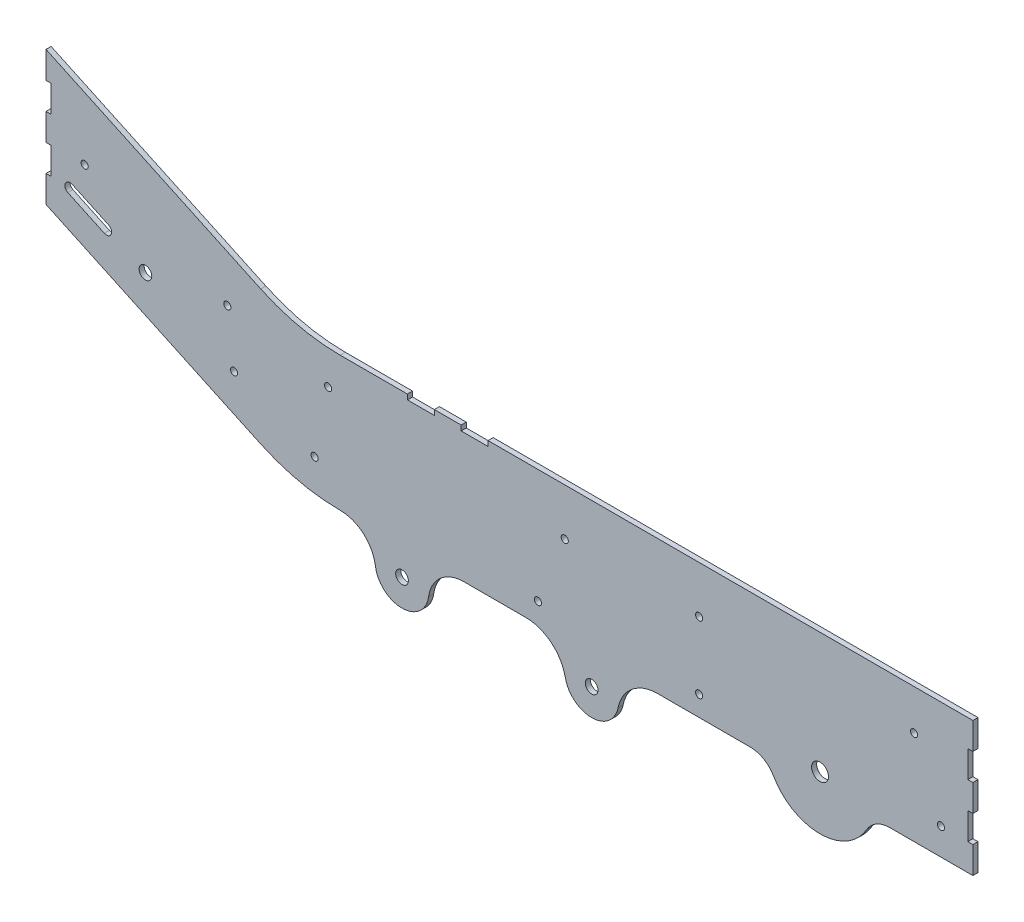
SolidWorks part; units mm, degrees
material "1060 Alloy"
ref_plane "Front Plane" through (0, 0, 0) normal (0, 0, 1) x (1, 0, 0)
ref_plane "Top Plane" through (0, 0, 0) normal (0, 1, 0) x (1, 0, 0)
ref_plane "Right Plane" through (0, 0, 0) normal (1, 0, 0) x (0, 0, -1)
sketch "standoff holes lower" plane through (0, 0, 0) normal (0, 0, 1) x (1, 0, 0)
  circle A7 centre (95.25, 85.725) radius 3.3782
  circle A8 centre (95.25, 12.7) radius 3.3782
  circle A9 centre (171.45, 12.7) radius 3.3782
  circle A10 centre (171.45, 85.725) radius 3.3782
  circle A12 centre (298.45, 12.7) radius 3.3782
  circle A13 centre (450.85, 85.725) radius 3.3782
  circle A16 centre (273.05, 85.725) radius 3.3782
  point P21 (0, 0)
sketch "axle holes lower" plane through (0, 0, 0) normal (0, 0, 1) x (1, 0, 0)
  line L10 (514.35, 98.425) -> (75.4368, 98.425) construction
  line L11 (66.0749, 94.3067) -> (3.3381, 25.8666) construction
  line L12 (0, 17.2849) -> (0, 12.7) construction
  line L13 (12.7, 0) -> (514.35, 0) construction
  line L14 (527.05, 12.7) -> (527.05, 85.725) construction
  circle A1 centre (247.65, 15.24) radius 4.826
  circle A4 centre (19.05, 19.05) radius 4.826
  arc A10 (527.05, 85.725) -> (514.35, 98.425) centre (514.35, 85.725) ccw construction
  arc A11 (75.4368, 98.425) -> (66.0749, 94.3067) centre (75.4368, 85.725) ccw construction
  arc A12 (3.3381, 25.8666) -> (0, 17.2849) centre (12.7, 17.2849) ccw construction
  arc A13 (0, 12.7) -> (12.7, 0) centre (12.7, 12.7) ccw construction
  arc A14 (514.35, 0) -> (527.05, 12.7) centre (514.35, 12.7) ccw construction
  circle A15 centre (476.25, 19.05) radius 4.826
sketch "lower box" plane through (0, 0, 0) normal (0, 0, 1) x (1, 0, 0)
  line L1 (622.3, 0) -> (-254, 0) construction
  line L2 (622.3, 0) -> (622.3, 25.4) construction
  line L3 (622.3, 127) -> (-254, 127) construction
  line L4 (-254, 0) -> (-254, 127) construction
  line L6 (527.05, 12.7) -> (527.05, 85.725) construction
  line L7 (622.3, 101.6) -> (622.3, 127) construction
  line L8 (622.3, 101.6) -> (617.474, 101.6) construction
  line L10 (622.3, 76.2) -> (617.474, 76.2) construction
  line L11 (617.474, 101.6) -> (617.474, 76.2) construction
  line L12 (622.3, 50.8) -> (617.474, 50.8) construction
  line L14 (622.3, 25.4) -> (617.474, 25.4) construction
  line L15 (617.474, 50.8) -> (617.474, 25.4) construction
  line L16 (622.3, 50.8) -> (622.3, 76.2) construction
  dimension "D1" = 127
  dimension "D2" = 876.3
  dimension "D3" = 95.25
  dimension "D4" = 4.826
sketch "alxe holes upper" plane through (0, 0, 0) normal (0, 0, 1) x (1, 0, 0)
  line L0 (-219.7848, 130.4205) -> (-230.5193, 107.4003) construction
  line L1 (-230.5193, 107.4003) -> (8.3155, -3.9702) construction
  line L3 (8.3155, -3.9702) -> (19.05, 19.05) construction
  line L4 (622.3, 0) -> (-254, 0) construction
  circle A0 centre (19.05, 19.05) radius 4.826 construction
  circle A2 centre (-219.7848, 130.4205) radius 4.826
  circle A3 centre (19.05, 19.05) radius 4.826
  dimension "D4" = 25
  dimension "D1" = 25.4
  dimension "D2" = 25.4
  dimension "D3" = 263.525
sketch "standoff holes upper" plane through (0, 0, 0) normal (0, 0, 1) x (1, 0, 0)
  line L0 (-162.9561, 84.3028) -> (-166.1764, 77.3967) construction
  line L1 (-226.6865, 105.613) -> (11.2395, -5.3337) construction
  line L4 (-37.2808, 64.9356) -> (-55.5295, 25.8012) construction
  line L5 (-230.5193, 107.4003) -> (8.3155, -3.9702) construction
  circle A2 centre (-162.9561, 84.3028) radius 3.3782
  circle A3 centre (-37.2808, 64.9356) radius 3.3782
  dimension "D2" = 7.62
  dimension "D1" = 43.18
sketch "upper shadow" plane through (0, 0, 0) normal (0, 0, 1) x (1, 0, 0)
  line L0 (-230.5193, 107.4003) -> (8.3155, -3.9702) construction
  line L4 (33.2535, 40.1076) -> (-204.2179, 150.8423) construction
  line L5 (-230.5193, 107.4003) -> (8.3155, -3.9702) construction
  arc A4 (8.3155, -3.9702) -> (33.2535, 40.1076) centre (19.05, 19.05) ccw construction
  arc A5 (-204.2179, 150.8423) -> (-230.5193, 107.4003) centre (-216.8161, 128.7868) ccw construction
  dimension "D1" = 25.4
  dimension "D2" = 25.4
sketch "upper box" plane through (0, 0, 0) normal (0, 0, 1) x (1, 0, 0)
  line L0 (-15.224, 0) -> (-254, 111.3431) construction
  line L1 (622.3, 0) -> (-254, 0) construction
  line L2 (-254, 111.3431) -> (-254, 136.7431) construction
  line L3 (-254, 238.3431) -> (257.1283, 0) construction
  line L4 (12.7, 0) -> (514.35, 0) construction
  line L5 (-254, 0) -> (-254, 127) construction
  line L6 (-230.5193, 107.4003) -> (8.3155, -3.9702) construction
  line L7 (-254, 212.9431) -> (-254, 238.3431) construction
  line L8 (-254, 212.9431) -> (-249.174, 212.9431) construction
  line L9 (-254, 162.1431) -> (-254, 187.5431) construction
  line L10 (-254, 187.5431) -> (-249.174, 187.5431) construction
  line L11 (-249.174, 212.9431) -> (-249.174, 187.5431) construction
  line L12 (-254, 162.1431) -> (-249.174, 162.1431) construction
  line L14 (-254, 136.7431) -> (-249.174, 136.7431) construction
  line L15 (-249.174, 162.1431) -> (-249.174, 136.7431) construction
  dimension "D1" = 127
  dimension "D2" = 6.35
  dimension "D3" = 4.826
sketch "outer face" plane through (0, 0, 0) normal (0, 0, 1) x (1, 0, 0)
  line L0 (622.3, 0) -> (-254, 0) construction
  line L1 (622.3, 0) -> (622.3, 25.4) construction
  line L2 (622.3, 25.4) -> (617.474, 25.4) construction
  line L3 (617.474, 50.8) -> (617.474, 25.4) construction
  line L4 (622.3, 50.8) -> (617.474, 50.8) construction
  line L5 (622.3, 50.8) -> (622.3, 76.2) construction
  line L6 (622.3, 76.2) -> (617.474, 76.2) construction
  line L7 (617.474, 101.6) -> (617.474, 76.2) construction
  line L8 (622.3, 101.6) -> (622.3, 127) construction
  line L9 (622.3, 101.6) -> (617.474, 101.6) construction
  line L10 (622.3, 127) -> (-254, 127) construction
  line L11 (-254, 238.3431) -> (257.1283, 0) construction
  line L12 (-254, 212.9431) -> (-254, 238.3431) construction
  line L13 (-254, 212.9431) -> (-249.174, 212.9431) construction
  line L14 (-249.174, 212.9431) -> (-249.174, 187.5431) construction
  line L15 (-249.174, 162.1431) -> (-249.174, 136.7431) construction
  line L16 (-254, 136.7431) -> (-249.174, 136.7431) construction
  line L17 (-254, 111.3431) -> (-254, 136.7431) construction
  line L18 (-15.224, 0) -> (-254, 111.3431) construction
  line L19 (-254, 162.1431) -> (-249.174, 162.1431) construction
  line L20 (-254, 162.1431) -> (-254, 187.5431) construction
  line L21 (-254, 187.5431) -> (-249.174, 187.5431) construction
  line L22 (622.3, 0) -> (24.1933, 0)
  line L23 (622.3, 0) -> (622.3, 25.4)
  line L24 (622.3, 25.4) -> (617.474, 25.4)
  line L25 (617.474, 50.8) -> (617.474, 25.4)
  line L26 (622.3, 50.8) -> (617.474, 50.8)
  line L27 (622.3, 50.8) -> (622.3, 76.2)
  line L28 (622.3, 76.2) -> (617.474, 76.2)
  line L29 (617.474, 101.6) -> (617.474, 76.2)
  line L30 (622.3, 101.6) -> (622.3, 127)
  line L31 (622.3, 101.6) -> (617.474, 101.6)
  line L32 (622.3, 127) -> (24.1933, 127)
  line L33 (-254, 238.3431) -> (-50.9483, 143.6585)
  line L34 (-254, 212.9431) -> (-254, 238.3431)
  line L35 (-254, 212.9431) -> (-249.174, 212.9431)
  line L36 (-249.174, 212.9431) -> (-249.174, 187.5431)
  line L37 (-249.174, 162.1431) -> (-249.174, 136.7431)
  line L38 (-254, 136.7431) -> (-249.174, 136.7431)
  line L39 (-254, 111.3431) -> (-254, 136.7431)
  line L40 (-50.9483, 16.6585) -> (-254, 111.3431)
  line L41 (-254, 162.1431) -> (-249.174, 162.1431)
  line L42 (-254, 162.1431) -> (-254, 187.5431)
  line L43 (-254, 187.5431) -> (-249.174, 187.5431)
  arc A0 (-50.9483, 16.6585) -> (24.1933, 0) centre (24.1933, 177.8) ccw
  arc A1 (24.1933, 127) -> (-50.9483, 143.6585) centre (24.1933, 304.8) cw
  dimension "D1" = 177.8
extrude "Boss-Extrude1" add sketch "outer face" along normal blind 4.826
sketch "Sketch5" plane through (0, 0, 4.826) normal (0, 0, 1) x (1, 0, 0)
  line L1 (-249.174, 162.1431) -> (-249.174, 136.7431) construction
  line L2 (622.3, 127) -> (24.1933, 127) construction
  line L4 (617.474, 76.2) -> (617.474, 101.6) construction
  line L5 (622.3, 127) -> (24.1933, 127) construction
  line L6 (414.2486, -29.6609) -> (414.2486, 95.7516) construction
  line L7 (24.1933, 0) -> (622.3, 0) construction
  line L8 (617.474, 25.4) -> (617.474, 50.8) construction
  circle A9 centre (-76.2, 63.5) radius 3.3782
  circle A10 centre (-82.55, 114.3) radius 3.3782
  circle A11 centre (592.074, 25.4) radius 3.3782
  circle A12 centre (0, 31.75) radius 3.3782
  circle A13 centre (211.0486, 19.05) radius 3.3782
  circle A14 centre (236.4486, 82.55) radius 3.3782
  circle A15 centre (363.4486, 82.55) radius 3.3782
  circle A16 centre (363.4486, 19.05) radius 3.3782
  circle A17 centre (566.674, 88.9) radius 3.3782
  circle A18 centre (12.7, 95.25) radius 3.3782
  circle A19 centre (-217.424, 162.1431) radius 3.3782
  dimension "D9" = 127
  dimension "D10" = 152.4
  dimension "D11" = 19.05
  dimension "D12" = 44.45
  dimension "D13" = 6.7564
  dimension "D7" = 19.05
  dimension "D14" = 25.4
  dimension "D15" = 25.4
  dimension "D17" = 31.75
  dimension "D16" = 82.55
  dimension "D18" = 82.55
  dimension "D19" = 76.2
  dimension "D20" = 31.75
  dimension "D21" = 31.75
  dimension "D22" = 50.8
  dimension "D23" = 63.5
  dimension "D24" = 12.7
  dimension "D3" = 38.1
  dimension "D4" = 50.8
  dimension "D5" = 44.45
  dimension "D6" = 50.8
  dimension "D8" = 50.8
extrude "standoff hole" cut sketch "Sketch5" against normal through all
sketch "Sketch6" plane through (0, 0, 4.826) normal (0, 0, 1) x (1, 0, 0)
  circle A0 centre (-219.7848, 130.4205) radius 4.826 construction
  circle A1 centre (19.05, 19.05) radius 4.826 construction
  circle A2 centre (247.65, 15.24) radius 4.826 construction
  circle A4 centre (-219.7848, 130.4205) radius 4.826
  circle A5 centre (19.05, 19.05) radius 4.826 construction
  circle A6 centre (247.65, 15.24) radius 4.826 construction
extrude "axle holes" cut sketch "Sketch6" against normal through all
sketch "Sketch7" plane through (0, 0, 4.826) normal (0, 0, 1) x (1, 0, 0)
  line L0 (-231.2949, 135.7877) -> (-196.7645, 119.686) construction
  line L1 (-229.2553, 140.1616) -> (-194.725, 124.0598)
  line L2 (-233.3344, 131.4139) -> (-198.8041, 115.3121)
  line L3 (-230.5193, 107.4003) -> (8.3155, -3.9702) construction
  circle A0 centre (-219.7848, 130.4205) radius 4.826 construction
  circle A1 centre (-219.7848, 130.4205) radius 4.826
  arc A2 (-229.2553, 140.1616) -> (-233.3344, 131.4139) centre (-231.2949, 135.7877) ccw
  arc A3 (-198.8041, 115.3121) -> (-194.725, 124.0598) centre (-196.7645, 119.686) ccw
  point P5 (-214.0297, 127.7369)
  circle M6 centre (-219.7848, 130.4205) radius 4.826
  dimension "D1" = 38.1
  dimension "D2" = 12.7
extrude "front slot" cut sketch "Sketch7" against normal through all contours L1 A2 L2 A1 M6 | L2 A3 L1 region at (-228.975, 134.706, 4.826) region at (-204.8394, 123.4514, 4.826)
sketch "Sketch8" plane through (0, 0, 4.826) normal (0, 0, 1) x (1, 0, 0)
  line L0 (113.0933, 127) -> (113.0933, 122.174) construction
  line L1 (87.6933, 122.174) -> (113.0933, 122.174)
  line L2 (87.6933, 122.174) -> (87.6933, 127)
  line L3 (87.6933, 127) -> (113.0933, 127)
  line L4 (113.0933, 122.174) -> (113.0933, 127)
  line L5 (622.3, 127) -> (24.1933, 127) construction
  line L6 (113.0933, 122.174) -> (138.4933, 122.174) construction
  line L7 (138.4933, 122.174) -> (163.8933, 122.174)
  line L8 (138.4933, 122.174) -> (138.4933, 127)
  line L9 (138.4933, 127) -> (163.8933, 127)
  line L10 (163.8933, 122.174) -> (163.8933, 127)
  line L11 (62.2933, 122.174) -> (189.2933, 122.174)
  line L12 (62.2933, 122.174) -> (62.2933, 127)
  line L13 (62.2933, 127) -> (189.2933, 127)
  line L14 (189.2933, 122.174) -> (189.2933, 127)
  line L15 (163.8933, 127) -> (163.8933, 122.174) construction
  point P18 (125.7933, 122.174)
  point P19 (125.7933, 122.174)
  line M29 (622.3, 127) -> (24.1933, 127)
  dimension "D1" = 127
extrude "top slots" cut sketch "Sketch8" against normal through all contours L1 L4 L2 M29 | L7 L10 L8 M29 region at (100.3933, 124.587, 4.826) region at (151.1933, 124.587, 4.826)
sketch "Sketch9" plane through (0, 0, 4.826) normal (0, 0, 1) x (1, 0, 0)
  line L0 (365.4629, -63.5) -> (553.974, -63.5) construction
  line L1 (24.1933, 0) -> (622.3, 0) construction
  line L3 (553.974, -63.5) -> (553.974, 63.787) construction
  line L4 (617.474, 25.4) -> (617.474, 50.8) construction
  line L5 (24.1933, 0) -> (622.3, 0)
  circle A0 centre (477.774, 12.7) radius 76.2 construction
  circle A1 centre (477.774, 12.7) radius 8
  arc A2 (433.7799, -12.7) -> (521.7681, -12.7) centre (477.774, 12.7) ccw
  arc A3 (543.7651, 0) -> (521.7681, -12.7) centre (543.7651, -25.4) ccw
  arc A4 (433.7799, -12.7) -> (411.7829, 0) centre (411.7829, -25.4) ccw
  dimension "D1" = 152.4
  dimension "D4" = 16
  dimension "D5" = 50.8
  dimension "D6" = 25.4
  dimension "D7" = 25.4
  dimension "D2" = 63.5
  dimension "D3" = 63.5
extrude "back axle extension" add sketch "Sketch9" against normal up to surface (4.826 mm away) contours A4 A2 A3 L5 region at (477.774, -15.4671, 4.826) up to face at (-214.0297, 127.7369, 0)
sketch "Sketch11" plane through (0, 0, 4.826) normal (0, 0, 1) x (1, 0, 0)
  line L0 (24.1933, 0) -> (411.7829, 0) construction
  line L1 (24.1933, 0) -> (411.7829, 0)
  line L2 (561.7812, -62.775) -> (321.8375, -62.775) construction
  line L3 (199.6366, 0) -> (324.1114, 0)
  arc A0 (471.7538, 87.9345) -> (489.1691, 87.3098) centre (477.774, 12.7) ccw construction
  arc A1 (471.7538, 87.9345) -> (489.1691, 87.3098) centre (477.774, 12.7) ccw
  circle A2 centre (261.874, -25.5) radius 37.275 construction
  arc A5 (258.0857, 11.582) -> (275.1308, 9.338) centre (261.874, -25.5) ccw construction
  arc A6 (258.0857, 11.582) -> (275.1308, 9.338) centre (261.874, -25.5) ccw construction
  arc A7 (236.9791, -30.54) -> (286.7689, -30.54) centre (261.874, -25.5) ccw
  arc A8 (324.1114, 0) -> (286.7689, -30.54) centre (324.1114, -38.1) ccw
  arc A9 (236.9791, -30.54) -> (199.6366, 0) centre (199.6366, -38.1) ccw
  dimension "D1" = 215.9
  dimension "D2" = 25.4
  dimension "D3" = 38.1
extrude "lower small axle extension" add sketch "Sketch11" against normal up to surface (4.826 mm away) contours A9 A7 A8 L1 region at (261.874, -20.0987, 4.826) up to face at (-214.0297, 127.7369, 0)
sketch "Sketch13" plane through (0, 0, 4.826) normal (0, 0, 1) x (1, 0, 0)
  line L0 (247.3066, -62.775) -> (540.2367, -62.775) construction
  line L1 (-361.4832, 140.4439) -> (-108.3874, 22.4235) construction
  line L2 (-229.2553, 140.1616) -> (-194.725, 124.0598) construction
  line L3 (24.1933, 0) -> (199.6366, 0) construction
  line L4 (24.1933, 0) -> (199.6366, 0)
  arc A0 (471.7538, 87.9345) -> (489.1691, 87.3098) centre (477.774, 12.7) ccw construction
  arc A1 (258.0857, 11.582) -> (275.1308, 9.338) centre (261.874, -25.5) ccw construction
  arc A2 (471.7538, 87.9345) -> (489.1691, 87.3098) centre (477.774, 12.7) ccw construction
  arc A3 (258.0857, 11.582) -> (275.1308, 9.338) centre (261.874, -25.5) ccw construction
  circle A5 centre (82.5849, -25.5) radius 37.275 construction
  arc A6 (-198.8041, 115.3121) -> (-194.725, 124.0598) centre (-196.7645, 119.686) ccw construction
  arc A7 (-198.8041, 115.3121) -> (-194.725, 124.0598) centre (-196.7645, 119.686) ccw construction
  circle A8 centre (-196.7645, 119.686) radius 50.8 construction
  arc A9 (57.4225, -28.9659) -> (107.7473, -28.9659) centre (82.5849, -25.5) ccw
  arc A12 (236.9791, -30.54) -> (286.7689, -30.54) centre (261.874, -25.5) ccw construction
  arc A13 (140.9765, 0) -> (107.7473, -28.9659) centre (140.9765, -33.543) ccw
  arc A14 (57.4225, -28.9659) -> (24.1933, 0) centre (24.1933, -33.543) ccw
  dimension "D1" = 101.6
extrude "front small axle extension" add sketch "Sketch13" against normal up to surface (4.826 mm away) contours A14 A9 A13 L4 region at (82.5849, -20.4486, 4.826) up to face at (-214.0297, 127.7369, 0)
sketch "Sketch14" plane through (0, 0, 4.826) normal (0, 0, 1) x (1, 0, 0)
  line L0 (-254, 111.3431) -> (-50.9483, 16.6585) construction
  line L1 (-254, 111.3431) -> (-50.9483, 16.6585)
  line L2 (-267.5177, 96.6271) -> (94.0166, -71.9591) construction
  line L3 (-227.5206, 77.9761) -> (-175.6892, 189.1288) construction
  arc A0 (78.7966, 11.582) -> (95.8417, 9.338) centre (82.5849, -25.5) ccw construction
  arc A1 (78.7966, 11.582) -> (95.8417, 9.338) centre (82.5849, -25.5) ccw
  circle A2 centre (-160.0111, 102.5476) radius 50.8 construction
  dimension "D1" = 101.6
  dimension "D2" = 38.1
sketch "Sketch10" plane through (0, 0, 4.826) normal (0, 0, 1) x (1, 0, 0)
  circle A0 centre (477.774, 12.7) radius 8
  circle A1 centre (261.874, -25.5) radius 6
  circle A2 centre (82.5849, -25.5) radius 6
  circle A3 centre (-160.0111, 102.5476) radius 6
  dimension "D1" = 16
  dimension "D2" = 12
  dimension "D3" = 12
extrude "new axle holes" cut sketch "Sketch10" against normal through all
equation "\"w\"= .19"
equation "\"D4@lower box\" = \"w\""
equation "\"D3@upper box\"=\"w\""
equation "\"D1@Boss-Extrude1\"=\"w\""
